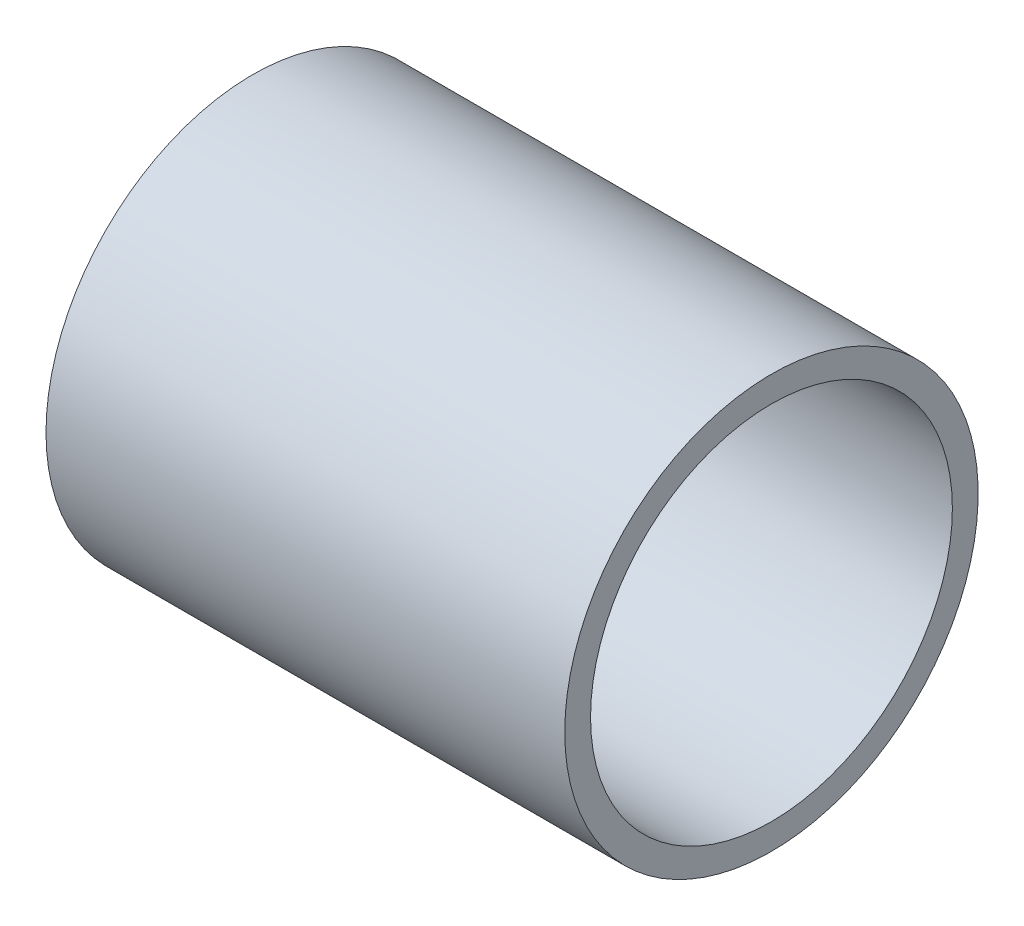
SolidWorks part; units mm, degrees
ref_plane "Front Plane" through (0, 0, 0) normal (0, 0, 1) x (1, 0, 0)
ref_plane "Top Plane" through (0, 0, 0) normal (0, 1, 0) x (1, 0, 0)
ref_plane "Right Plane" through (0, 0, 0) normal (1, 0, 0) x (0, 0, -1)
sketch "Sketch2" plane through (0, 0, 0) normal (0, 0, 1) x (1, 0, 0)
  line L0 (0, 0) -> (74.8146, 0) construction
  line L2 (0, 141.732) -> (406.4, 141.732)
  line L3 (0, 141.732) -> (0, 161.925)
  line L4 (0, 161.925) -> (406.4, 161.925)
  line L5 (406.4, 141.732) -> (406.4, 161.925)
  dimension "D1" = 141.732
  dimension "D3" = 406.4
  dimension "D2" = 161.925
revolve "Revolve1" add sketch "Sketch2" angle 360 about L0
ref_plane "Midplane" through (203.2, 0, 0) normal (-1, 0, 0) x (0, 0, 1)
equation "\"ID\"= 11.160in"
equation "\"OD\"= 12.75in"
equation "\"Length\"= 16in"
equation "\"D1@Sketch2\"=\"ID\"/2"
equation "\"D3@Sketch2\"=\"Length\""
equation "\"D2@Sketch2\"=\"OD\"/2"
